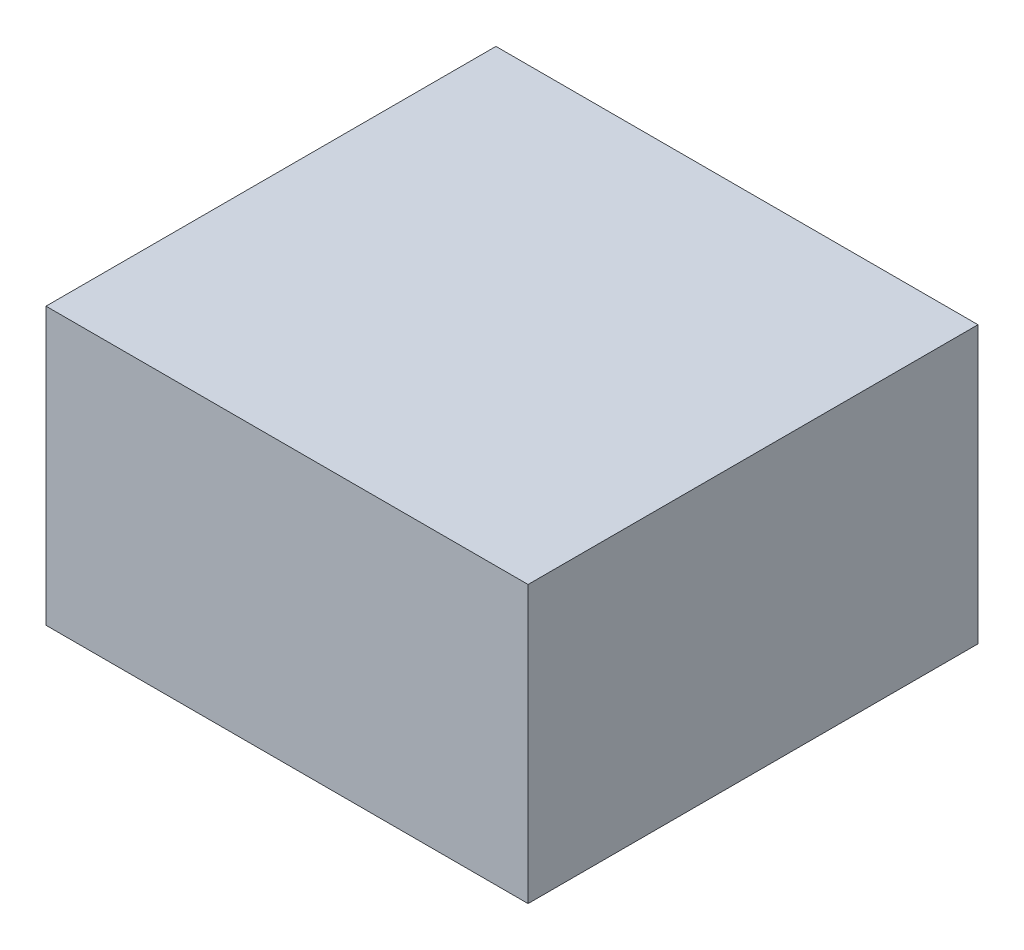
SolidWorks part; units mm, degrees
ref_plane "Front Plane" through (0, 0, 0) normal (0, 0, 1) x (1, 0, 0)
ref_plane "Top Plane" through (0, 0, 0) normal (0, 1, 0) x (1, 0, 0)
ref_plane "Right Plane" through (0, 0, 0) normal (1, 0, 0) x (0, 0, -1)
sketch "Sketch1" plane through (0, 0, 0) normal (0, 1, 0) x (1, 0, 0)
  line L0 (-75, 70) -> (75, -70) construction
  line L1 (-75, 70) -> (75, 70)
  line L2 (-75, 70) -> (-75, -70)
  line L3 (-75, -70) -> (75, -70)
  line L4 (75, 70) -> (75, -70)
  line L5 (74, 69) -> (74, -69)
  line L6 (-74, -69) -> (74, -69)
  line L7 (-74, 69) -> (-74, -69)
  line L8 (-74, 69) -> (74, 69)
  dimension "D1" = 140
  dimension "D2" = 150
  dimension "D3" = 1
extrude "Boss-Extrude1" add sketch "Sketch1" along normal blind 43 and the other way blind 43
sketch "Sketch3" plane through (0, 43, 0) normal (0, 1, 0) x (1, 0, 0)
  line L2 (-75, 70) -> (75, 70)
  line L3 (-75, 70) -> (-75, -70)
  line L4 (-75, -70) -> (75, -70)
  line L5 (75, 70) -> (75, -70)
  point P2 (-75, 70)
extrude "Boss-Extrude2" add sketch "Sketch3" against normal blind 1
sketch "Sketch4" plane through (0, -43, 0) normal (0, -1, 0) x (1, 0, 0)
  line L1 (-75, 70) -> (75, 70)
  line L2 (-75, 70) -> (-75, -70)
  line L3 (-75, -70) -> (75, -70)
  line L4 (75, 70) -> (75, -70)
extrude "Boss-Extrude3" add sketch "Sketch4" against normal blind 1
sketch "Sketch2" plane through (0, 0, -70) normal (0, 0, -1) x (-1, 0, 0)
  line L0 (-23, 43) -> (-23, -43) construction
  line L1 (-75, 43) -> (75, 43) construction
  line L2 (-23, 0) -> (0, 0) construction
  line L3 (-75, -43) -> (-75, 43) construction
  line L4 (-30.5, 12.9904) -> (-33.5, 18.1865) construction
  line L5 (-44.0941, 38.5) -> (-35.5698, 38.5)
  line L6 (-61.5, 21.0941) -> (-61.5, 12.5698)
  line L7 (-1.9059, 38.5) -> (-10.4302, 38.5)
  line L8 (15.5, 21.0941) -> (15.5, 12.5698)
  line L9 (-109.3914, 49.8781) -> (63.3914, -49.8781) construction
  line L10 (-33.5, 18.1865) -> (-34.75, 20.3516) construction
  line L11 (-34.75, 20.3516) -> (-37.75, 25.5477) construction
  line L12 (-37.75, 25.5477) -> (-39, 27.7128) construction
  line L13 (-39, 27.7128) -> (-42, 32.909) construction
  line L14 (-42, 32.909) -> (-43.25, 35.074) construction
  line L15 (-38.0935, 8.7142) -> (-37.3435, 10.0133) construction
  line L16 (-109.3914, -49.8781) -> (63.3914, 49.8781) construction
  line L17 (-60.2463, 23.2362) -> (-35.1753, 8.7614) construction
  line L18 (-30.5, 12.9904) -> (-23, 0) construction
  line L19 (-43.25, 35.074) -> (-44.95, 38.0185) construction
  line L20 (15.5, -21.0941) -> (15.5, -12.5698)
  line L21 (-1.9059, -38.5) -> (-10.4302, -38.5)
  line L22 (-44.0941, -38.5) -> (-35.5698, -38.5)
  line L23 (-61.5, -21.0941) -> (-61.5, -12.5698)
  line L24 (-75, -43) -> (75, -43) construction
  line L25 (-69, 37.5) -> (-69, -26.5) construction
  line L26 (0, 0) -> (0, 62.9533) construction
  line L27 (75, -43) -> (75, 43) construction
  line L28 (28, -1.5) -> (62, -1.5) construction
  line L29 (25, -19) -> (65, -19) construction
  line L30 (44.25, -0.75) -> (45.75, -0.75)
  line L31 (45, -0.75) -> (45, -2.25) construction
  line L32 (43.2396, 1) -> (44.25, -0.75)
  line L33 (40.3529, 1) -> (43.2396, 1)
  line L34 (38.9095, -1.5) -> (40.3529, 1)
  line L35 (51.0905, -1.5) -> (49.6471, -4)
  line L36 (49.6471, -4) -> (46.7604, -4)
  line L37 (51.0905, -1.5) -> (49.6471, 1)
  line L38 (49.6471, 1) -> (46.7604, 1)
  line L39 (46.7604, 1) -> (45.75, -0.75)
  line L40 (46.7604, -4) -> (45.75, -2.25)
  line L41 (44.25, -2.25) -> (45.75, -2.25)
  line L42 (43.2396, -4) -> (44.25, -2.25)
  line L43 (40.3529, -4) -> (43.2396, -4)
  line L44 (51.5229, -0.751) -> (52.5094, 0.9576) [skipped]
  line L45 (45.2334, -1.3552) -> (46.2199, -3.0638) [skipped]
  line L46 (38.9095, -1.5) -> (40.3529, -4)
  line L48 (47.4386, -4) -> (51.3845, -4) [skipped]
  line L49 (33.5, -28.5) -> (56.5, -28.5)
  line L50 (31.5, -26.5) -> (31.5, -11.5)
  line L51 (33.5, -9.5) -> (56.5, -9.5)
  line L52 (58.5, -26.5) -> (58.5, -11.5)
  line L53 (31.5, -28.5) -> (58.5, -9.5) construction
  line L54 (31.5, -9.5) -> (58.5, -28.5) construction
  arc A0 (-35.5698, 38.5) -> (-61.5, 12.5698) centre (-23, 0) ccw
  arc A1 (-37.984, 14.7132) -> (-33.7029, 10.5094) centre (-35.8435, 12.6113) ccw
  arc A2 (-23, 18) -> (-32, 15.5885) centre (-23, 0) ccw construction
  arc A3 (-38.5885, 9) -> (-32, 15.5885) centre (-23, 0) cw construction
  arc A4 (-45.672, 18.8741) -> (-41.0607, 15.0353) centre (-43.3664, 16.9547) ccw
  arc A5 (-53.193, 23.0735) -> (-48.4257, 19.4303) centre (-50.8093, 21.2519) ccw
  arc A6 (-27.8857, 37.6846) -> (-27.1143, 31.7344) centre (-27.5, 34.7095) cw
  arc A7 (-26.75, 14.5237) -> (-33.7029, 10.5094) centre (-23, 0) ccw
  arc A8 (-28.25, 20.3332) -> (-37.984, 14.7132) centre (-23, 0) ccw
  arc A9 (-26.9906, 23.1587) -> (-41.0607, 15.0353) centre (-23, 0) ccw
  arc A10 (-28.0094, 29.0716) -> (-45.672, 18.8741) centre (-23, 0) ccw
  arc A11 (-27.1143, 31.7344) -> (-48.4257, 19.4303) centre (-23, 0) ccw
  arc A12 (-27.8857, 37.6846) -> (-53.193, 23.0735) centre (-23, 0) ccw
  arc A13 (-44.0941, 38.5) -> (-61.5, 21.0941) centre (-23, 0) ccw
  arc A14 (-28.0094, 29.0716) -> (-26.9906, 23.1587) centre (-27.5, 26.1151) cw
  arc A15 (-28.25, 20.3332) -> (-26.75, 14.5237) centre (-27.5, 17.4284) cw
  arc A16 (-12.2971, 10.5094) -> (-19.25, 14.5237) centre (-23, 0) ccw
  arc A17 (-8.016, 14.7132) -> (-12.2971, 10.5094) centre (-10.1565, 12.6113) cw
  arc A18 (-8.016, 14.7132) -> (-17.75, 20.3332) centre (-23, 0) ccw
  arc A19 (-17.75, 20.3332) -> (-19.25, 14.5237) centre (-18.5, 17.4284) ccw
  arc A20 (-17.9906, 29.0716) -> (-19.0094, 23.1587) centre (-18.5, 26.1151) ccw
  arc A21 (-4.9393, 15.0353) -> (-19.0094, 23.1587) centre (-23, 0) ccw
  arc A22 (-0.328, 18.8741) -> (-17.9906, 29.0716) centre (-23, 0) ccw
  arc A23 (-0.328, 18.8741) -> (-4.9393, 15.0353) centre (-2.6336, 16.9547) cw
  arc A24 (7.193, 23.0735) -> (2.4257, 19.4303) centre (4.8093, 21.2519) cw
  arc A25 (2.4257, 19.4303) -> (-18.8857, 31.7344) centre (-23, 0) ccw
  arc A26 (7.193, 23.0735) -> (-18.1143, 37.6846) centre (-23, 0) ccw
  arc A27 (-18.1143, 37.6846) -> (-18.8857, 31.7344) centre (-18.5, 34.7095) ccw
  arc A28 (-8.5471, -4.0142) -> (-8.5471, 4.0142) centre (-23, 0) ccw
  arc A29 (-2.766, -5.6199) -> (-8.5471, -4.0142) centre (-5.6565, -4.8171) cw
  arc A30 (-2.766, -5.6199) -> (-2.766, 5.6199) centre (-23, 0) ccw
  arc A31 (-2.766, 5.6199) -> (-8.5471, 4.0142) centre (-5.6565, 4.8171) ccw
  arc A32 (4.6814, 10.1975) -> (-0.9487, 8.1234) centre (1.8664, 9.1605) ccw
  arc A33 (-0.9487, -8.1234) -> (-0.9487, 8.1234) centre (-23, 0) ccw
  arc A34 (4.6814, -10.1975) -> (4.6814, 10.1975) centre (-23, 0) ccw
  arc A35 (4.6814, -10.1975) -> (-0.9487, -8.1234) centre (1.8664, -9.1605) cw
  arc A36 (12.0787, -14.6112) -> (6.5399, -12.3041) centre (9.3093, -13.4576) cw
  arc A37 (6.5399, -12.3041) -> (6.5399, 12.3041) centre (-23, 0) ccw
  arc A38 (12.0787, -14.6112) -> (12.0787, 14.6112) centre (-23, 0) ccw
  arc A39 (12.0787, 14.6112) -> (6.5399, 12.3041) centre (9.3093, 13.4576) ccw
  arc A40 (-19.25, -14.5237) -> (-12.2971, -10.5094) centre (-23, 0) ccw
  arc A41 (-17.75, -20.3332) -> (-19.25, -14.5237) centre (-18.5, -17.4284) cw
  arc A42 (-17.75, -20.3332) -> (-8.016, -14.7132) centre (-23, 0) ccw
  arc A43 (-8.016, -14.7132) -> (-12.2971, -10.5094) centre (-10.1565, -12.6113) ccw
  arc A44 (-0.328, -18.8741) -> (-4.9393, -15.0353) centre (-2.6336, -16.9547) ccw
  arc A45 (-19.0094, -23.1587) -> (-4.9393, -15.0353) centre (-23, 0) ccw
  arc A46 (-17.9906, -29.0716) -> (-0.328, -18.8741) centre (-23, 0) ccw
  arc A47 (-17.9906, -29.0716) -> (-19.0094, -23.1587) centre (-18.5, -26.1151) cw
  arc A48 (-18.1143, -37.6846) -> (-18.8857, -31.7344) centre (-18.5, -34.7095) cw
  arc A49 (-18.8857, -31.7344) -> (2.4257, -19.4303) centre (-23, 0) ccw
  arc A50 (-18.1143, -37.6846) -> (7.193, -23.0735) centre (-23, 0) ccw
  arc A51 (7.193, -23.0735) -> (2.4257, -19.4303) centre (4.8093, -21.2519) ccw
  arc A52 (-33.7029, -10.5094) -> (-26.75, -14.5237) centre (-23, 0) ccw
  arc A53 (-37.984, -14.7132) -> (-33.7029, -10.5094) centre (-35.8435, -12.6113) cw
  arc A54 (-37.984, -14.7132) -> (-28.25, -20.3332) centre (-23, 0) ccw
  arc A55 (-28.25, -20.3332) -> (-26.75, -14.5237) centre (-27.5, -17.4284) ccw
  arc A56 (-28.0094, -29.0716) -> (-26.9906, -23.1587) centre (-27.5, -26.1151) ccw
  arc A57 (-41.0607, -15.0353) -> (-26.9906, -23.1587) centre (-23, 0) ccw
  arc A58 (-45.672, -18.8741) -> (-28.0094, -29.0716) centre (-23, 0) ccw
  arc A59 (-45.672, -18.8741) -> (-41.0607, -15.0353) centre (-43.3664, -16.9547) cw
  arc A60 (-53.193, -23.0735) -> (-48.4257, -19.4303) centre (-50.8093, -21.2519) cw
  arc A61 (-48.4257, -19.4303) -> (-27.1143, -31.7344) centre (-23, 0) ccw
  arc A62 (-53.193, -23.0735) -> (-27.8857, -37.6846) centre (-23, 0) ccw
  arc A63 (-27.8857, -37.6846) -> (-27.1143, -31.7344) centre (-27.5, -34.7095) ccw
  arc A64 (-37.4529, 4.0142) -> (-37.4529, -4.0142) centre (-23, 0) ccw
  arc A65 (-43.234, 5.6199) -> (-37.4529, 4.0142) centre (-40.3435, 4.8171) cw
  arc A66 (-43.234, 5.6199) -> (-43.234, -5.6199) centre (-23, 0) ccw
  arc A67 (-43.234, -5.6199) -> (-37.4529, -4.0142) centre (-40.3435, -4.8171) ccw
  arc A68 (-50.6814, -10.1975) -> (-45.0513, -8.1234) centre (-47.8664, -9.1605) ccw
  arc A69 (-45.0513, 8.1234) -> (-45.0513, -8.1234) centre (-23, 0) ccw
  arc A70 (-50.6814, 10.1975) -> (-50.6814, -10.1975) centre (-23, 0) ccw
  arc A71 (-50.6814, 10.1975) -> (-45.0513, 8.1234) centre (-47.8664, 9.1605) cw
  arc A72 (-58.0787, 14.6112) -> (-52.5399, 12.3041) centre (-55.3093, 13.4576) cw
  arc A73 (-52.5399, 12.3041) -> (-52.5399, -12.3041) centre (-23, 0) ccw
  arc A74 (-58.0787, 14.6112) -> (-58.0787, -14.6112) centre (-23, 0) ccw
  arc A75 (-58.0787, -14.6112) -> (-52.5399, -12.3041) centre (-55.3093, -13.4576) ccw
  arc A76 (-1.9059, 38.5) -> (15.5, 21.0941) centre (-23, 0) cw
  arc A77 (-10.4302, 38.5) -> (15.5, 12.5698) centre (-23, 0) cw
  arc A78 (-1.9059, -38.5) -> (15.5, -21.0941) centre (-23, 0) ccw
  arc A79 (-10.4302, -38.5) -> (15.5, -12.5698) centre (-23, 0) ccw
  arc A80 (-44.0941, -38.5) -> (-61.5, -21.0941) centre (-23, 0) cw
  arc A81 (-35.5698, -38.5) -> (-61.5, -12.5698) centre (-23, 0) cw
  circle A82 centre (-69, 37.5) radius 1.5
  circle A83 centre (-69, -26.5) radius 1.5
  circle A84 centre (69, 37.5) radius 1.5
  circle A85 centre (45, -37.5) radius 1.5
  circle A86 centre (-59, 36) radius 2.5
  circle A87 centre (13, 36) radius 2.5
  circle A88 centre (13, -36) radius 2.5
  circle A89 centre (-59, -36) radius 2.5
  circle A90 centre (28, -1.5) radius 2
  circle A91 centre (62, -1.5) radius 2
  circle A92 centre (25, -19) radius 1
  circle A93 centre (65, -19) radius 1
  arc A94 (56.5, -9.5) -> (58.5, -11.5) centre (56.5, -11.5) cw
  arc A95 (50.7037, -1.5) -> (46.0387, -0.25) centre (48.2037, -1.5) ccw construction
  arc A96 (33.5, -28.5) -> (31.5, -26.5) centre (33.5, -26.5) cw
  arc A97 (31.5, -11.5) -> (33.5, -9.5) centre (33.5, -11.5) cw
  arc A98 (56.5, -28.5) -> (58.5, -26.5) centre (56.5, -26.5) ccw
  point P143 (-23, 0)
  point P183 (45, -19)
  point P204 (45, -1.5)
  point P212 (35.3102, -14.2874)
  dimension "D1" = 15
  dimension "D6" = 2.5
  dimension "D7" = 6
  dimension "D8" = 1.5
  dimension "D9" = 3.4
  dimension "D10" = 38.5
  dimension "D11" = 6
  dimension "D14" = 3
  dimension "D18" = 5
  dimension "D21" = 4
  dimension "D25" = 2
  dimension "D31" = 2
  dimension "D2" = 52
  dimension "D3" = 4.5
  dimension "D4" = 60
  dimension "D5" = 60
  dimension "D12" = 5.5
  dimension "D13" = 6
  dimension "D15" = 16.5
  dimension "D16" = 30
  dimension "D17" = 5.5
  dimension "D19" = 44.5
  dimension "D20" = 47
  dimension "D22" = 13
  dimension "D23" = 24
  dimension "D24" = 40
  dimension "D26" = 10
  dimension "D27" = 2.5
  dimension "D28" = 0.75
  dimension "D29" = 19
  dimension "D30" = 27
extrude "Cut-Extrude1" cut sketch "Sketch2" against normal blind 1
